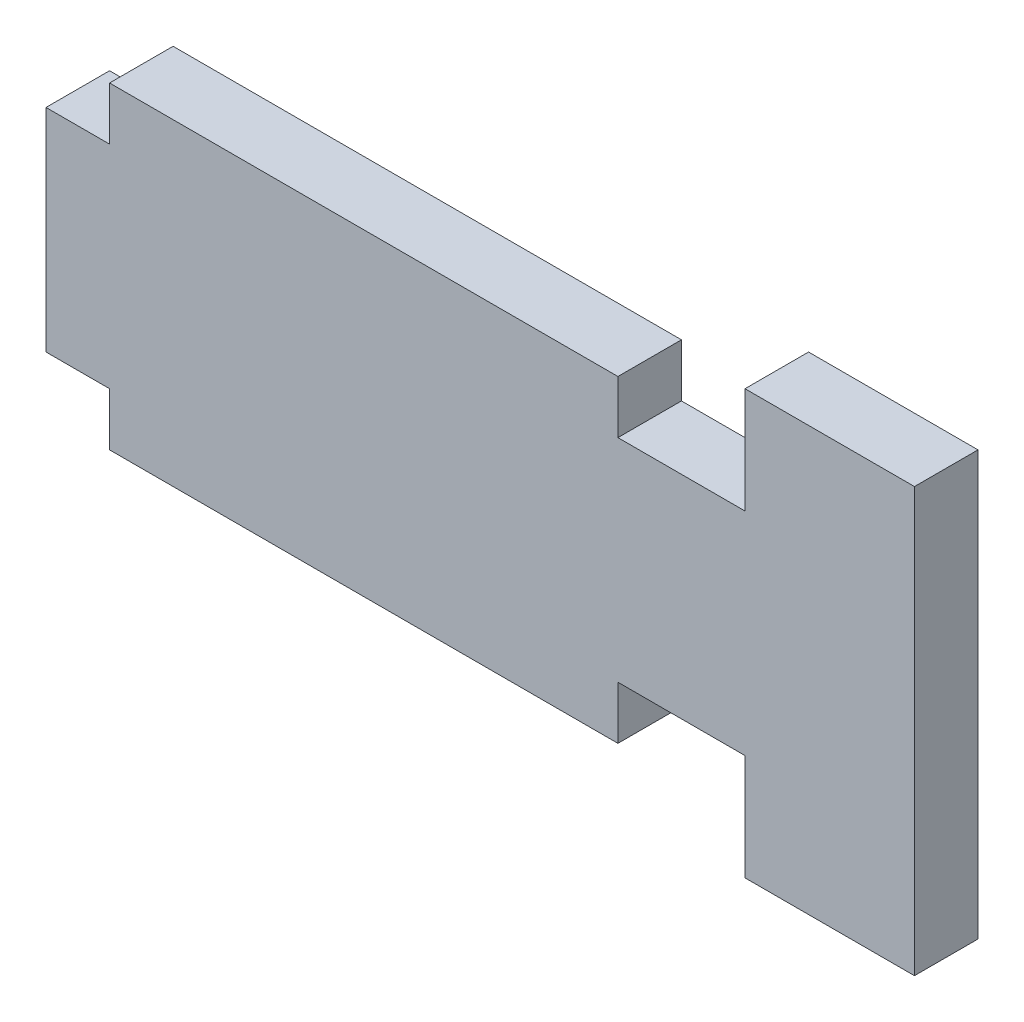
SolidWorks part; units mm, degrees
material "MDF"
ref_plane "Plano frontal" through (0, 0, 0) normal (0, 0, 1) x (1, 0, 0)
ref_plane "Plano superior" through (0, 0, 0) normal (0, 1, 0) x (1, 0, 0)
ref_plane "Plano direito" through (0, 0, 0) normal (1, 0, 0) x (0, 0, -1)
sketch "Esboço1" plane through (0, 0, 0) normal (0, 0, 1) x (1, 0, 0)
  line L0 (0, 0) -> (12, 0) construction
  line L1 (-12, -7.5) -> (12, -7.5)
  line L2 (-12, -7.5) -> (-12, 7.5)
  line L3 (-12, 7.5) -> (12, 7.5)
  line L4 (12, -7.5) -> (12, 7.5)
  line L5 (-12, -7.5) -> (12, 7.5) construction
  line L6 (-12, 7.5) -> (12, -7.5) construction
  line L11 (0, 0) -> (0, -7.5) construction
  line L12 (-15, -5) -> (-12, -5)
  line L17 (-15, -5) -> (-15, 5)
  line L18 (-15, 5) -> (-12, 5)
  line L19 (-12, -5) -> (-12, 5)
  line L20 (-15, -5) -> (-12, 5) construction
  line L21 (-15, 5) -> (-12, -5) construction
  line L26 (18, 5) -> (12, 5)
  line L27 (12, -5) -> (12, 5)
  line L28 (18, -5) -> (12, -5)
  line L29 (18, -5) -> (18, 5)
  line L30 (18, 5) -> (18, 10)
  line L31 (18, 10) -> (26, 10)
  line L32 (26, 10) -> (26, -10)
  line L33 (26, -10) -> (18, -10)
  line L34 (18, -5) -> (18, -10)
  point P0 (0, 0)
  point P6 (-13.5, 0)
  point P7 (26, 0)
  dimension "D5" = 6
  dimension "D1" = 15
  dimension "D2" = 3
  dimension "D3" = 10
  dimension "D4" = 24
  dimension "D6" = 8
  dimension "D7" = 20
extrude "Ressalto-extrusão1" add sketch "Esboço1" along normal blind 3 contours L18 L17 L12 L2 | L28 L4 L3 L2 L1 | L28 L29 L26 L4 | L29 L34 L33 L32 L31 L30 | L17 L12 L19 L18 region at (0, 0, 0) region at (-13.5, 0, 0) region at (15, 0, 0) region at (22, 0, 0)
